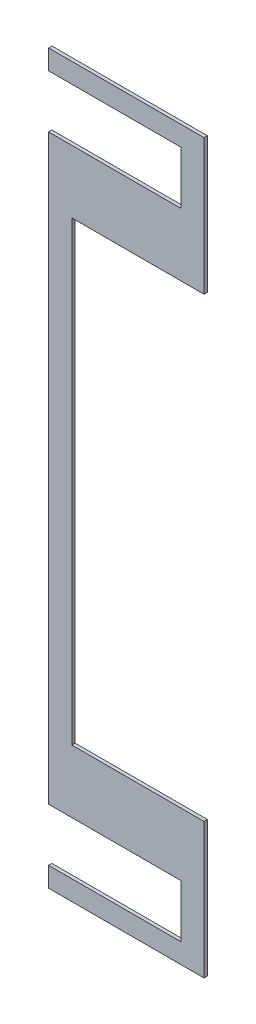
SolidWorks part; units mm, degrees
ref_plane "Front Plane" through (0, 0, 0) normal (1, 0, 0) x (0, 1, 0)
ref_plane "Top Plane" through (0, 0, 0) normal (0, 0, 1) x (0, 1, 0)
ref_plane "Right Plane" through (0, 0, 0) normal (0, 1, 0) x (-1, 0, 0)
sketch "Sketch1" plane through (0, 0, 0) normal (0, 0, 1) x (0, 1, 0)
  line L0 (568.325, 0) -> (568.325, -22.225) construction
  line L1 (0, 0) -> (19.05, 0) construction
  line L2 (0, 0) -> (0, -149.225) construction
  line L3 (0, -149.225) -> (19.05, -149.225) construction
  line L4 (19.05, 0) -> (19.05, -149.225) construction
  line L5 (19.05, -149.225) -> (69.85, -149.225) construction
  line L6 (19.05, -149.225) -> (19.05, -127) construction
  line L7 (19.05, -127) -> (69.85, -127) construction
  line L8 (69.85, -149.225) -> (69.85, -127) construction
  line L9 (69.85, -149.225) -> (130.175, -149.225) construction
  line L10 (69.85, -149.225) -> (69.85, 0) construction
  line L11 (69.85, 0) -> (130.175, 0) construction
  line L12 (130.175, -149.225) -> (130.175, 0) construction
  line L13 (130.175, 0) -> (568.325, 0) construction
  line L14 (130.175, 0) -> (130.175, -22.225) construction
  line L15 (130.175, -22.225) -> (568.325, -22.225) construction
  line L16 (349.25, 0) -> (349.25, -22.225) construction
  line L17 (568.325, -149.225) -> (568.325, 0) construction
  line L18 (628.65, 0) -> (568.325, 0) construction
  line L19 (628.65, -149.225) -> (628.65, 0) construction
  line L20 (628.65, -149.225) -> (568.325, -149.225) construction
  line L21 (628.65, -149.225) -> (628.65, -127) construction
  line L22 (679.45, -127) -> (628.65, -127) construction
  line L23 (679.45, -149.225) -> (679.45, -127) construction
  line L24 (679.45, -149.225) -> (628.65, -149.225) construction
  line L25 (679.45, 0) -> (679.45, -149.225) construction
  line L26 (698.5, -149.225) -> (679.45, -149.225) construction
  line L27 (698.5, 0) -> (698.5, -149.225) construction
  line L28 (698.5, 0) -> (679.45, 0) construction
  line L29 (0, 0) -> (0, -149.225)
  line L30 (0, -149.225) -> (130.175, -149.225)
  line L31 (130.175, -149.225) -> (130.175, -22.225)
  line L32 (130.175, -22.225) -> (568.325, -22.225)
  line L33 (568.325, -22.225) -> (568.325, -149.225)
  line L34 (568.325, -149.225) -> (698.5, -149.225)
  line L35 (698.5, -149.225) -> (698.5, 0)
  line L36 (698.5, 0) -> (679.45, 0)
  line L37 (679.45, 0) -> (679.45, -127)
  line L38 (679.45, -127) -> (628.65, -127)
  line L39 (628.65, -127) -> (628.65, 0)
  line L40 (628.65, 0) -> (69.85, 0)
  line L41 (69.85, 0) -> (69.85, -127)
  line L42 (69.85, -127) -> (19.05, -127)
  line L43 (19.05, -127) -> (19.05, 0)
  line L44 (19.05, 0) -> (0, 0)
  dimension "D1" = 149.225
  dimension "D2" = 19.05
  dimension "D3" = 22.225
  dimension "D4" = 50.8
  dimension "D5" = 60.325
  dimension "D6" = 279.4
  dimension "D7" = 22.225
extrude "Boss-Extrude1" add sketch "Sketch1" along normal blind 3.175
